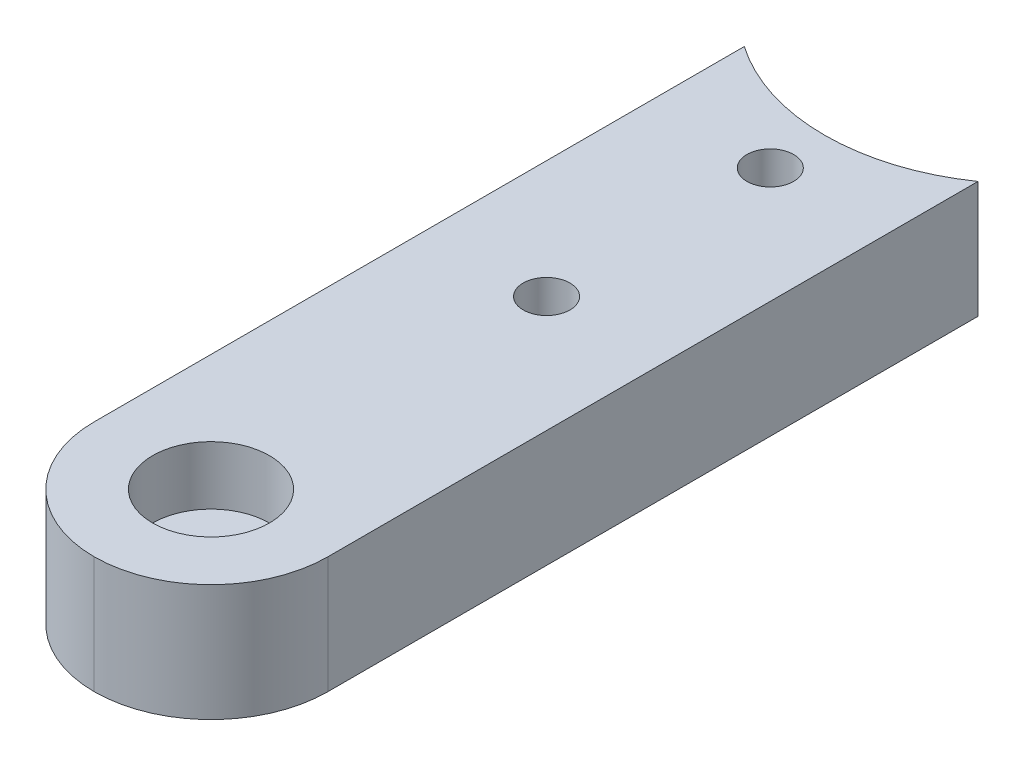
SolidWorks part; units mm, degrees
ref_plane "前视基准面" through (0, 0, 0) normal (0, 0, 1) x (1, 0, 0)
ref_plane "上视基准面" through (0, 0, 0) normal (0, 1, 0) x (1, 0, 0)
ref_plane "右视基准面" through (0, 0, 0) normal (1, 0, 0) x (0, 0, -1)
other "Configuration Table"
sketch "草图1" plane through (0, 0, 0) normal (0, 1, 0) x (1, 0, 0)
  line L0 (2, 0) -> (2, -2) construction
  line L1 (0, 0) -> (4, 0)
  line L2 (0, 0) -> (0, -15)
  line L3 (0, -15) -> (4, -15)
  line L4 (4, 0) -> (4, -15)
  dimension "D1" = 2
  dimension "D2" = 4
  dimension "32.4" = 15
extrude "凸台-拉伸1" add sketch "草图1" along normal blind 2
sketch "草图3" plane through (0, 2, 0) normal (0, 1, 0) x (1, 0, 0)
  line L0 (4, -13) -> (2, -13) construction
  line L1 (4, 0) -> (4, -15) construction
  line L2 (2, -13) -> (0, -13) construction
  line L3 (0, 0) -> (0, -15) construction
  line L4 (0, -15) -> (4, -15) construction
  circle A0 centre (2, -13) radius 0.4
  circle A3 centre (2, -13) radius 1
  circle A4 centre (2.0225, -3.45) radius 0.4
  circle A7 centre (2.0135, -7.27) radius 0.4
  point P17 (0, 0)
  dimension "D3" = 2
  dimension "D4" = 0.8
  dimension "D5" = 0.8
  dimension "D1" = 2
extrude "切除-拉伸1" cut sketch "草图3" against normal through all contours A4 | A0 | A7
extrude "切除-拉伸2" cut sketch "草图3<3>" against normal offset from surface (1 mm away) 1 contours A3 up to face at (2.0225, 0, 3.85)
sketch "草图3<3>" plane through (0, 2, 0) normal (0, 1, 0) x (1, 0, 0) same geometry as "草图3"
sketch "草图4" plane through (0, 2, 0) normal (0, 1, 0) x (1, 0, 0)
  line L0 (0, 0) -> (4, 0) construction
  line L1 (2, -15) -> (2, 1) construction
  line L2 (0, -15) -> (4, -15) construction
  circle A0 centre (2, 1) radius 3.5
  dimension "D2" = 7
  dimension "D1" = 1
extrude "切除-拉伸3" cut sketch "草图4" against normal through all
fillet "圆角1" radius 2 2 edges at (4, 1, 15) (0, 1, 15)
